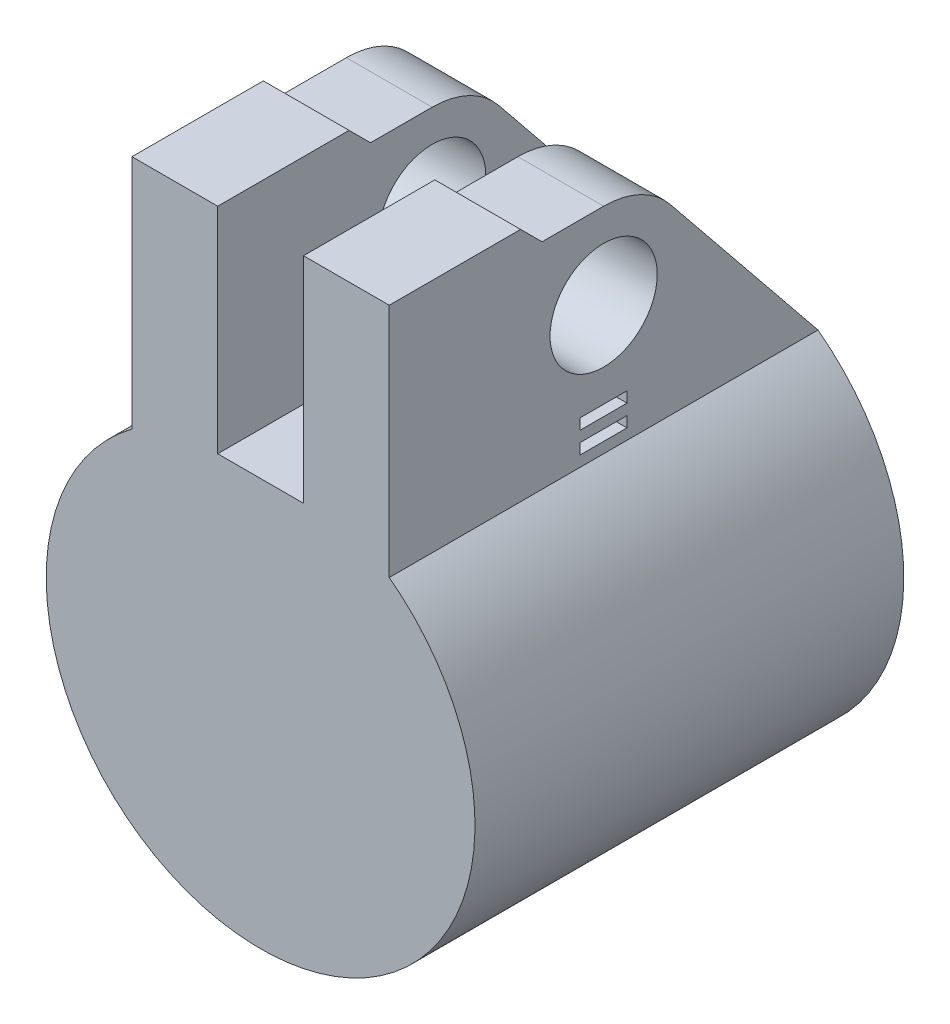
SolidWorks part; units mm, degrees
ref_plane "Front Plane" through (0, 0, 0) normal (0, 0, 1) x (1, 0, 0)
ref_plane "Top Plane" through (0, 0, 0) normal (0, 1, 0) x (1, 0, 0)
ref_plane "Right Plane" through (0, 0, 0) normal (1, 0, 0) x (0, 0, -1)
sketch "Sketch1" plane through (0, 0, 0) normal (0, 0, 1) x (1, 0, 0)
  line L0 (-93.8958, 25.0575) -> (-78.6558, 25.0575)
  arc A0 (-93.8958, 25.0575) -> (-78.6558, 25.0575) centre (-86.2758, 14.8975) ccw
extrude "Boss-Extrude2" add sketch "Sketch1" along normal blind 25.4
sketch "Sketch5" plane through (0, 25.0575, 0) normal (0, 1, 0) x (1, 0, 0)
  line L1 (-93.8958, 0) -> (-78.6558, 0)
  line L2 (-93.8958, 0) -> (-93.8958, -25.4)
  line L3 (-93.8958, -25.4) -> (-78.6558, -25.4)
  line L4 (-78.6558, 0) -> (-78.6558, -25.4)
extrude "Boss-Extrude3" add sketch "Sketch5" along normal blind 12.7
sketch "Sketch7" plane through (0, 37.7575, 0) normal (0, 1, 0) x (1, 0, 0)
  line L0 (-93.8958, -25.4) -> (-78.6558, -25.4) construction
  line L1 (-83.7358, -25.4) -> (-88.8158, -25.4)
  line L2 (-83.7358, -25.4) -> (-83.7358, 0)
  line L3 (-83.7358, 0) -> (-88.8158, 0)
  line L4 (-88.8158, -25.4) -> (-88.8158, 0)
  line L5 (-78.6558, 0) -> (-93.8958, 0) construction
  line L6 (-78.6558, -25.4) -> (-78.6558, 0) construction
  line L7 (-93.8958, 0) -> (-93.8958, -25.4) construction
  dimension "D1" = 5.08
  dimension "D2" = 5.08
extrude "Cut-Extrude1" cut sketch "Sketch7" against normal blind 11.43
sketch "Sketch8" plane through (-78.6558, 0, 0) normal (1, 0, 0) x (0, 0, -1)
  line L0 (-25.4, 37.7575) -> (-25.4, 25.0575) construction
  line L1 (-25.4, 37.7575) -> (0, 37.7575) construction
  line L2 (-25.4, 37.7575) -> (0, 37.7575) construction
  line L3 (-12.7, 37.7575) -> (0, 37.7575)
  line L4 (0, 37.7575) -> (0, 25.0575)
  line L5 (-8.7508, 35.8728) -> (0, 25.0575)
  circle A0 centre (-12.7, 32.6775) radius 3.175
  arc A1 (-12.7, 37.7575) -> (-8.7508, 35.8728) centre (-12.7, 32.6775) cw
  dimension "D1" = 12.7
  dimension "D3" = 6.35
  dimension "D2" = 5.08
extrude "Cut-Extrude2" cut sketch "Sketch8" against normal blind 17.018
sketch "Sketch9" plane through (0, 26.3275, 0) normal (0, 1, 0) x (1, 0, 0)
  line L0 (-88.8158, -12.7) -> (-88.8158, -25.4) construction
  line L3 (-88.8158, -25.4) -> (-83.7358, -25.4) construction
  circle A0 centre (-86.2758, -12.7) radius 2.54
  dimension "D1" = 2.54
  dimension "D2" = 12.7
extrude "Cut-Extrude3" cut sketch "Sketch9" against normal through all
sketch "Sketch10" plane through (0, 37.7575, 0) normal (0, 1, 0) x (1, 0, 0)
  line L0 (-93.8958, -12.7) -> (-93.8958, -25.4) construction
  line L1 (-93.8958, -16.3495) -> (-88.8158, -16.3495)
  line L2 (-93.8958, -16.3495) -> (-93.8958, -25.4)
  line L3 (-93.8958, -25.4) -> (-88.8158, -25.4)
  line L4 (-88.8158, -16.3495) -> (-88.8158, -25.4)
  line L5 (-83.7358, -25.4) -> (-83.7358, -12.7) construction
  line L6 (-83.7358, -16.3495) -> (-78.6558, -16.3495)
  line L7 (-83.7358, -16.3495) -> (-83.7358, -25.4)
  line L8 (-83.7358, -25.4) -> (-78.6558, -25.4)
  line L9 (-78.6558, -16.3495) -> (-78.6558, -25.4)
extrude "Boss-Extrude4" add sketch "Sketch10" along normal blind 1.27
chamfer "Chamfer1" distance 1.27 angle 45 2 edges at (-81.1958, 39.0275, 16.3495) (-91.3558, 39.0275, 16.3495)
ref_plane "Plane1" through (0, 0, 12.7) normal (0, 0, 1) x (1, 0, 0)
sketch "Sketch11" plane through (0, 0, 12.7) normal (0, 0, 1) x (1, 0, 0)
  line L0 (-88.8158, 26.3275) -> (-93.0009, 4.1242)
  line L2 (-88.8158, 26.3275) -> (-83.7358, 26.3275)
  line L3 (-83.7358, 26.3275) -> (-79.5507, 4.1242)
  arc A0 (-93.8958, 25.0575) -> (-78.6558, 25.0575) centre (-86.2758, 14.8975) ccw construction
  arc A1 (-93.0009, 4.1242) -> (-79.5507, 4.1242) centre (-86.2758, 14.8975) ccw
extrude "Cut-Extrude4" cut sketch "Sketch11" against normal blind 2.54 and the other way blind 2.54
sketch "Sketch12" plane through (-78.6558, 0, 0) normal (1, 0, 0) x (0, 0, -1)
  line L0 (-12.7, 13.97) -> (-12.7, -13.97) construction
  line L1 (-14.0854, 25.6925) -> (-11.3146, 25.6925)
  line L2 (-14.0854, 25.6925) -> (-14.0854, 26.3275)
  line L3 (-14.0854, 26.3275) -> (-11.3146, 26.3275)
  line L4 (-11.3146, 25.6925) -> (-11.3146, 26.3275)
  line L5 (-14.0854, 25.6925) -> (-11.3146, 26.3275) construction
  line L6 (-14.0854, 26.3275) -> (-11.3146, 25.6925) construction
  line L7 (-25.4, 25.0575) -> (0, 25.0575) construction
  line L8 (-14.0854, 26.9625) -> (-11.3146, 26.9625)
  line L9 (-14.0854, 26.9625) -> (-14.0854, 27.5975)
  line L10 (-14.0854, 27.5975) -> (-11.3146, 27.5975)
  line L11 (-11.3146, 26.9625) -> (-11.3146, 27.5975)
  line L12 (-14.0854, 26.9625) -> (-11.3146, 27.5975) construction
  line L13 (-14.0854, 27.5975) -> (-11.3146, 26.9625) construction
  point P0 (-12.7, 26.01)
  point P7 (-12.7, 27.28)
  dimension "D1" = 0.635
  dimension "D2" = 1.27
  dimension "D3" = 0.635
  dimension "D4" = 0.635
extrude "Cut-Extrude5" cut sketch "Sketch12" against normal through all
